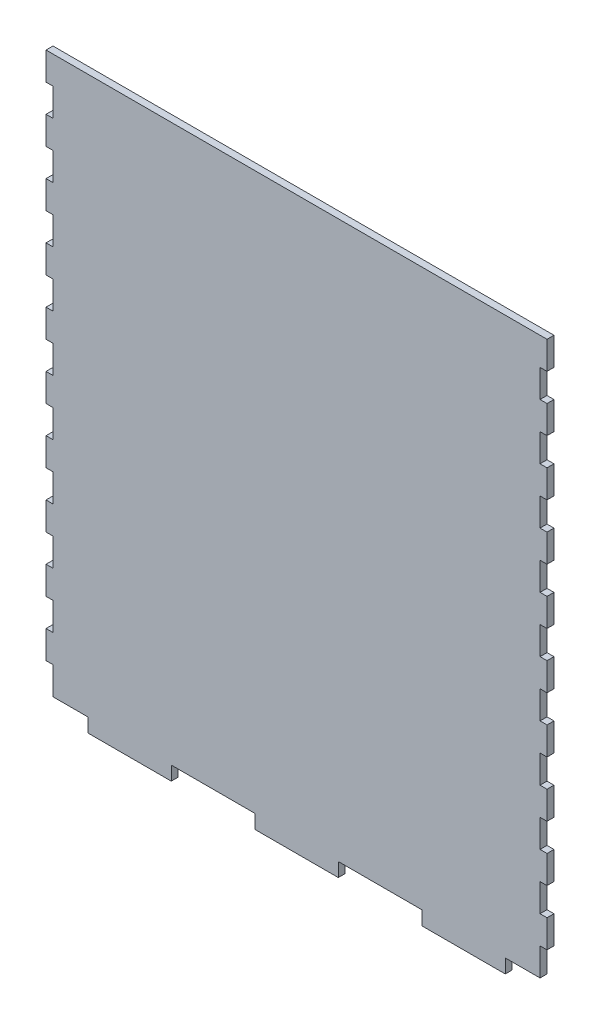
SolidWorks part; units mm, degrees
material "Acrylic (Medium-high impact)"
ref_plane "Front Plane" through (0, 0, 0) normal (0, 0, 1) x (1, 0, 0)
ref_plane "Top Plane" through (0, 0, 0) normal (0, 1, 0) x (1, 0, 0)
ref_plane "Right Plane" through (0, 0, 0) normal (1, 0, 0) x (0, 0, -1)
sketch "Sketch1" plane through (0, 0, 0) normal (0, 0, 1) x (1, 0, 0)
  line L0 (-114.3, 114.3) -> (-111.125, 114.3)
  line L1 (-114.3, 127) -> (114.3, 127)
  line L2 (-114.3, 127) -> (-114.3, -127)
  line L3 (-114.3, -127) -> (114.3, -127)
  line L4 (114.3, 127) -> (114.3, -127)
  line L5 (-114.3, 127) -> (-111.125, 127)
  line L6 (-114.3, 127) -> (-114.3, 114.3)
  line L7 (-114.3, 114.3) -> (-111.125, 114.3)
  line L8 (-111.125, 127) -> (-111.125, 114.3)
  line L9 (-114.3, 114.3) -> (-114.3, 101.6)
  line L10 (-114.3, 101.6) -> (-111.125, 101.6)
  line L11 (-111.125, 114.3) -> (-111.125, 101.6)
  line L12 (-114.3, 101.6) -> (-111.125, 101.6)
  line L13 (-114.3, 101.6) -> (-114.3, 88.9)
  line L14 (-114.3, 88.9) -> (-111.125, 88.9)
  line L15 (-111.125, 101.6) -> (-111.125, 88.9)
  line L16 (-114.3, 88.9) -> (-111.125, 88.9)
  line L17 (-114.3, 88.9) -> (-114.3, 76.2)
  line L18 (-114.3, 76.2) -> (-111.125, 76.2)
  line L19 (-111.125, 88.9) -> (-111.125, 76.2)
  line L20 (-114.3, 76.2) -> (-111.125, 76.2)
  line L21 (-114.3, 76.2) -> (-114.3, 63.5)
  line L22 (-114.3, 63.5) -> (-111.125, 63.5)
  line L23 (-111.125, 76.2) -> (-111.125, 63.5)
  line L24 (-114.3, 63.5) -> (-111.125, 63.5)
  line L25 (-114.3, 63.5) -> (-114.3, 50.8)
  line L26 (-114.3, 50.8) -> (-111.125, 50.8)
  line L27 (-111.125, 63.5) -> (-111.125, 50.8)
  line L28 (-114.3, 50.8) -> (-111.125, 50.8)
  line L29 (-114.3, 50.8) -> (-114.3, 38.1)
  line L30 (-114.3, 38.1) -> (-111.125, 38.1)
  line L31 (-111.125, 50.8) -> (-111.125, 38.1)
  line L32 (-114.3, 38.1) -> (-111.125, 38.1)
  line L33 (-114.3, 38.1) -> (-114.3, 25.4)
  line L34 (-114.3, 25.4) -> (-111.125, 25.4)
  line L35 (-111.125, 38.1) -> (-111.125, 25.4)
  line L36 (-114.3, 25.4) -> (-111.125, 25.4)
  line L37 (-114.3, 25.4) -> (-114.3, 12.7)
  line L38 (-114.3, 12.7) -> (-111.125, 12.7)
  line L39 (-111.125, 25.4) -> (-111.125, 12.7)
  line L40 (-114.3, 12.7) -> (-111.125, 12.7)
  line L41 (-114.3, 12.7) -> (-114.3, 0)
  line L42 (-114.3, 0) -> (-111.125, 0)
  line L43 (-111.125, 12.7) -> (-111.125, 0)
  line L44 (-114.3, 0) -> (-111.125, 0)
  line L45 (-114.3, 0) -> (-114.3, -12.7)
  line L46 (-114.3, -12.7) -> (-111.125, -12.7)
  line L47 (-111.125, 0) -> (-111.125, -12.7)
  line L48 (-114.3, -12.7) -> (-111.125, -12.7)
  line L49 (-114.3, -12.7) -> (-114.3, -25.4)
  line L50 (-114.3, -25.4) -> (-111.125, -25.4)
  line L51 (-111.125, -12.7) -> (-111.125, -25.4)
  line L52 (-114.3, -25.4) -> (-111.125, -25.4)
  line L53 (-114.3, -25.4) -> (-114.3, -38.1)
  line L54 (-114.3, -38.1) -> (-111.125, -38.1)
  line L55 (-111.125, -25.4) -> (-111.125, -38.1)
  line L56 (-114.3, -38.1) -> (-111.125, -38.1)
  line L57 (-114.3, -38.1) -> (-114.3, -50.8)
  line L58 (-114.3, -50.8) -> (-111.125, -50.8)
  line L59 (-111.125, -38.1) -> (-111.125, -50.8)
  line L60 (-114.3, -50.8) -> (-111.125, -50.8)
  line L61 (-114.3, -50.8) -> (-114.3, -63.5)
  line L62 (-114.3, -63.5) -> (-111.125, -63.5)
  line L63 (-111.125, -50.8) -> (-111.125, -63.5)
  line L64 (-114.3, -63.5) -> (-111.125, -63.5)
  line L65 (-114.3, -63.5) -> (-114.3, -76.2)
  line L66 (-114.3, -76.2) -> (-111.125, -76.2)
  line L67 (-111.125, -63.5) -> (-111.125, -76.2)
  line L68 (-114.3, -76.2) -> (-111.125, -76.2)
  line L69 (-114.3, -76.2) -> (-114.3, -88.9)
  line L70 (-114.3, -88.9) -> (-111.125, -88.9)
  line L71 (-111.125, -76.2) -> (-111.125, -88.9)
  line L72 (-114.3, -88.9) -> (-111.125, -88.9)
  line L73 (-114.3, -88.9) -> (-114.3, -101.6)
  line L74 (-114.3, -101.6) -> (-111.125, -101.6)
  line L75 (-111.125, -88.9) -> (-111.125, -101.6)
  line L76 (-114.3, -101.6) -> (-111.125, -101.6)
  line L77 (-114.3, -101.6) -> (-114.3, -114.3)
  line L78 (-114.3, -114.3) -> (-111.125, -114.3)
  line L79 (-111.125, -101.6) -> (-111.125, -114.3)
  line L80 (-114.3, -114.3) -> (-111.125, -114.3)
  line L81 (-114.3, -114.3) -> (-114.3, -127)
  line L82 (-114.3, -127) -> (-111.125, -127)
  line L83 (-111.125, -114.3) -> (-111.125, -127)
  line L100 (0, 127) -> (0, -127) construction
  line L101 (114.3, 114.3) -> (111.125, 114.3)
  line L102 (114.3, 127) -> (111.125, 127)
  line L103 (114.3, 127) -> (114.3, 114.3)
  line L104 (114.3, 114.3) -> (111.125, 114.3)
  line L105 (111.125, 127) -> (111.125, 114.3)
  line L106 (114.3, 114.3) -> (114.3, 101.6)
  line L107 (114.3, 101.6) -> (111.125, 101.6)
  line L108 (111.125, 114.3) -> (111.125, 101.6)
  line L109 (114.3, 101.6) -> (111.125, 101.6)
  line L110 (114.3, 101.6) -> (114.3, 88.9)
  line L111 (114.3, 88.9) -> (111.125, 88.9)
  line L112 (111.125, 101.6) -> (111.125, 88.9)
  line L113 (114.3, 88.9) -> (111.125, 88.9)
  line L114 (114.3, 88.9) -> (114.3, 76.2)
  line L115 (114.3, 76.2) -> (111.125, 76.2)
  line L116 (111.125, 88.9) -> (111.125, 76.2)
  line L117 (114.3, 76.2) -> (111.125, 76.2)
  line L118 (114.3, 76.2) -> (114.3, 63.5)
  line L119 (114.3, 63.5) -> (111.125, 63.5)
  line L120 (111.125, 76.2) -> (111.125, 63.5)
  line L121 (114.3, 63.5) -> (111.125, 63.5)
  line L122 (114.3, 63.5) -> (114.3, 50.8)
  line L123 (114.3, 50.8) -> (111.125, 50.8)
  line L124 (111.125, 63.5) -> (111.125, 50.8)
  line L125 (114.3, 50.8) -> (111.125, 50.8)
  line L126 (114.3, 50.8) -> (114.3, 38.1)
  line L127 (114.3, 38.1) -> (111.125, 38.1)
  line L128 (111.125, 50.8) -> (111.125, 38.1)
  line L129 (114.3, 38.1) -> (111.125, 38.1)
  line L130 (114.3, 38.1) -> (114.3, 25.4)
  line L131 (114.3, 25.4) -> (111.125, 25.4)
  line L132 (111.125, 38.1) -> (111.125, 25.4)
  line L133 (114.3, 25.4) -> (111.125, 25.4)
  line L134 (114.3, 25.4) -> (114.3, 12.7)
  line L135 (114.3, 12.7) -> (111.125, 12.7)
  line L136 (111.125, 25.4) -> (111.125, 12.7)
  line L137 (114.3, 12.7) -> (111.125, 12.7)
  line L138 (114.3, 12.7) -> (114.3, 0)
  line L139 (114.3, 0) -> (111.125, 0)
  line L140 (111.125, 12.7) -> (111.125, 0)
  line L141 (114.3, 0) -> (111.125, 0)
  line L142 (114.3, 0) -> (114.3, -12.7)
  line L143 (114.3, -12.7) -> (111.125, -12.7)
  line L144 (111.125, 0) -> (111.125, -12.7)
  line L145 (114.3, -12.7) -> (111.125, -12.7)
  line L146 (114.3, -12.7) -> (114.3, -25.4)
  line L147 (114.3, -25.4) -> (111.125, -25.4)
  line L148 (111.125, -12.7) -> (111.125, -25.4)
  line L149 (114.3, -25.4) -> (111.125, -25.4)
  line L150 (114.3, -25.4) -> (114.3, -38.1)
  line L151 (114.3, -38.1) -> (111.125, -38.1)
  line L152 (111.125, -25.4) -> (111.125, -38.1)
  line L153 (114.3, -38.1) -> (111.125, -38.1)
  line L154 (114.3, -38.1) -> (114.3, -50.8)
  line L155 (114.3, -50.8) -> (111.125, -50.8)
  line L156 (111.125, -38.1) -> (111.125, -50.8)
  line L157 (114.3, -50.8) -> (111.125, -50.8)
  line L158 (114.3, -50.8) -> (114.3, -63.5)
  line L159 (114.3, -63.5) -> (111.125, -63.5)
  line L160 (111.125, -50.8) -> (111.125, -63.5)
  line L161 (114.3, -63.5) -> (111.125, -63.5)
  line L162 (114.3, -63.5) -> (114.3, -76.2)
  line L163 (114.3, -76.2) -> (111.125, -76.2)
  line L164 (111.125, -63.5) -> (111.125, -76.2)
  line L165 (114.3, -76.2) -> (111.125, -76.2)
  line L166 (114.3, -76.2) -> (114.3, -88.9)
  line L167 (114.3, -88.9) -> (111.125, -88.9)
  line L168 (111.125, -76.2) -> (111.125, -88.9)
  line L169 (114.3, -88.9) -> (111.125, -88.9)
  line L170 (114.3, -88.9) -> (114.3, -101.6)
  line L171 (114.3, -101.6) -> (111.125, -101.6)
  line L172 (111.125, -88.9) -> (111.125, -101.6)
  line L173 (114.3, -101.6) -> (111.125, -101.6)
  line L174 (114.3, -101.6) -> (114.3, -114.3)
  line L175 (114.3, -114.3) -> (111.125, -114.3)
  line L176 (111.125, -101.6) -> (111.125, -114.3)
  line L177 (114.3, -114.3) -> (111.125, -114.3)
  line L178 (114.3, -114.3) -> (114.3, -127)
  line L179 (114.3, -127) -> (111.125, -127)
  line L180 (111.125, -114.3) -> (111.125, -127)
  line L183 (95.25, -127) -> (95.25, -133.35)
  line L184 (95.25, -133.35) -> (57.15, -133.35)
  line L185 (57.15, -133.35) -> (57.15, -127)
  line L186 (57.15, -127) -> (95.25, -127)
  line L188 (-19.05, -127) -> (19.05, -127)
  line L189 (19.05, -127) -> (19.05, -133.35)
  line L190 (19.05, -133.35) -> (-19.05, -133.35)
  line L191 (-19.05, -133.35) -> (-19.05, -127)
  line L192 (-95.25, -127) -> (-57.15, -127)
  line L193 (-57.15, -127) -> (-57.15, -133.35)
  line L194 (-57.15, -133.35) -> (-95.25, -133.35)
  line L195 (-95.25, -133.35) -> (-95.25, -127)
  point P4 (0, 127)
  point P6 (-114.3, 0)
  dimension "D1" = 254
  dimension "D2" = 228.6
  dimension "D3" = 12.7
  dimension "D4" = 3.175
  dimension "D7" = 6.35
  dimension "D8" = 38.1
  dimension "D9" = 19.05
  dimension "D11" = 19.05
  dimension "D5" = 20
  dimension "D6" = 20
  dimension "D10" = 3
extrude "Boss-Extrude1" add sketch "Sketch1" along normal blind 3.175 contours L100 L1 L8 L11 L15 L19 L23 L27 L31 L35 L39 L43 L47 L51 L55 L59 L63 L67 L71 L75 L79 L83 L3 | L1 L100 L3 L180 L176 L172 L168 L164 L160 L156 L152 L148 L144 L140 L136 L132 L128 L124 L120 L116 L112 L108 L105 | L1 L105 L101 L4 | L107 L112 L111 L4 | L115 L120 L119 L4 | L123 L128 L127 L4 | L131 L136 L135 L4 | L139 L144 L143 L4 | L147 L152 L151 L4 | L155 L160 L159 L4 | L163 L168 L167 L4 | L171 L176 L175 L4 | L8 L1 L2 L0 | L15 L10 L2 L14 | L23 L18 L2 L22 | L31 L26 L2 L30 | L63 L58 L2 L62 | L71 L66 L2 L70 | L79 L74 L2 L78 | L185 L184 L183 L3 | L191 L190 L189 L188 L3 | L195 L194 L193 L3 | L39 L38 L37 L36 | L47 L46 L45 L44 | L55 L54 L53 L52 region at (-112.7125, 120.65, 0) region at (-55.5625, 0, 0) region at (-112.7125, 95.25, 0) region at (55.5625, 0, 0) region at (-112.7125, 69.85, 0) region at (112.7125, 120.65, 0) region at (0, -130.175, 0) region at (-112.7125, 44.45, 0) region at (112.7125, 95.25, 0) region at (-76.2, -130.175, 0) region at (76.2, -130.175, 0) region at (112.7125, 69.85, 0) region at (-112.7125, -107.95, 0) region at (112.7125, -107.95, 0) region at (112.7125, 44.45, 0) region at (-112.7125, -82.55, 0) region at (112.7125, -82.55, 0) region at (112.7125, 19.05, 0) region at (-112.7125, -57.15, 0) region at (112.7125, -57.15, 0) region at (112.7125, -6.35, 0) region at (112.7125, -31.75, 0)
